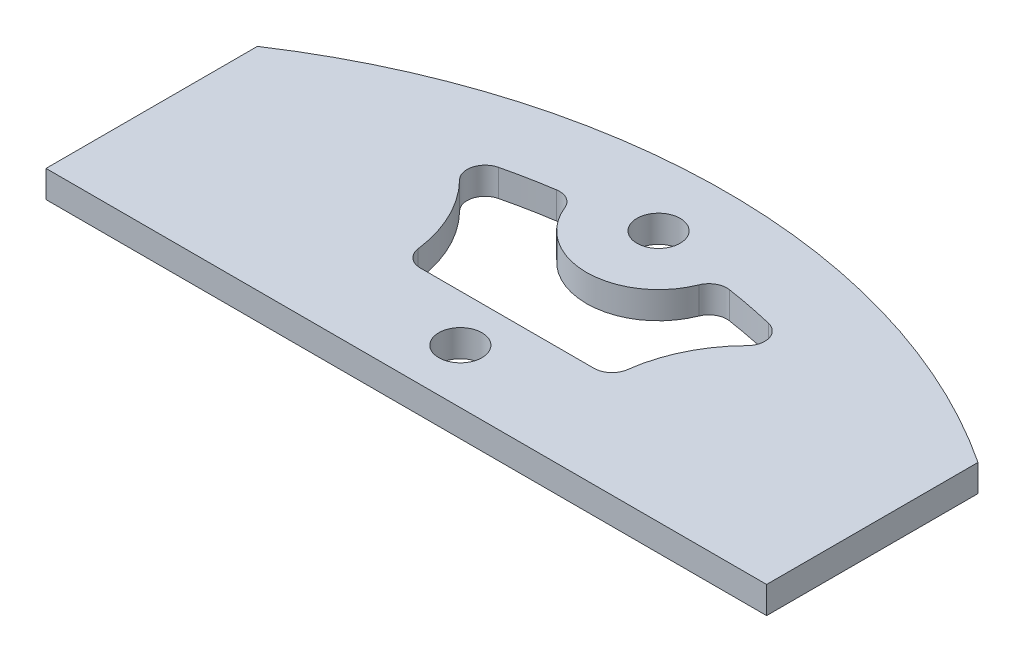
SolidWorks part; units mm, degrees
material "Acrylic (Medium-high impact)"
ref_plane "Front Plane" through (0, 0, 0) normal (0, 0, 1) x (1, 0, 0)
ref_plane "Top Plane" through (0, 0, 0) normal (0, 1, 0) x (1, 0, 0)
ref_plane "Right Plane" through (0, 0, 0) normal (1, 0, 0) x (0, 0, -1)
sketch "Sketch1" plane through (0, 0, 0) normal (0, 1, 0) x (1, 0, 0)
  line L0 (0, -85) -> (-32.4891, -64.8129) construction
  line L1 (0, -85) -> (0, 0) construction
  arc A0 (36.5434, -62.6165) -> (-36.5434, -62.6165) centre (0, 0) ccw
  arc A1 (30.0898, -61.3851) -> (-30.0898, -61.3851) centre (0, -85) ccw
  arc A2 (36.5434, -62.6165) -> (30.0898, -61.3851) centre (34.0231, -58.2982) cw
  arc A3 (-30.0898, -61.3851) -> (-36.5434, -62.6165) centre (-34.0231, -58.2982) cw
  dimension "D1" = 145
  dimension "D2" = 76.5
  dimension "D4" = 5
  dimension "D3" = 85
extrude "Boss-Extrude1" add sketch "Sketch1" along normal blind 3
sketch "Sketch13" plane through (0, 3, 0) normal (0, 1, 0) x (1, 0, 0)
  line L10 (-11.5013, 48.2) -> (11.5013, 48.2)
  line L11 (-9.6388, 48.2) -> (9.6388, 48.2)
  arc A8 (14.9949, 62.2186) -> (15.9519, 58.8715) centre (14.5263, 60.2743) cw
  arc A9 (7.4323, 62.04) -> (9.59, 63.2774) centre (9.2903, 61.3) cw
  arc A10 (9.6388, 48.2) -> (11.623, 49.9486) centre (9.6388, 50.2) ccw
  arc A11 (-9.6388, 48.2) -> (-11.623, 49.9486) centre (-9.6388, 50.2) cw
  arc A28 (-9.59, 63.2774) -> (-7.4323, 62.04) centre (-9.2903, 61.3) cw
  arc A29 (-11.5013, 48.2) -> (-18.8249, 61.1688) centre (-27, 48) ccw
  arc A30 (-7.861, 63.5154) -> (-18.8249, 61.1688) centre (0, 0) ccw
  arc A31 (-7.861, 63.5154) -> (7.861, 63.5154) centre (0, 65) ccw
  arc A32 (18.8249, 61.1688) -> (7.861, 63.5154) centre (0, 0) ccw
  arc A33 (18.8249, 61.1688) -> (11.5013, 48.2) centre (27, 48) ccw
  arc A34 (-11.623, 49.9486) -> (-15.9519, 58.8715) centre (-27, 48) ccw
  arc A35 (-9.59, 63.2774) -> (-14.9949, 62.2186) centre (0, 0) ccw
  arc A36 (-7.4323, 62.04) -> (7.4323, 62.04) centre (0, 65) ccw
  arc A37 (14.9949, 62.2186) -> (9.59, 63.2774) centre (0, 0) ccw
  arc A38 (15.9519, 58.8715) -> (11.623, 49.9486) centre (27, 48) ccw
  arc A39 (-15.9519, 58.8715) -> (-14.9949, 62.2186) centre (-14.5263, 60.2743) cw
  dimension "D2" = 2
  dimension "D1" = 0
extrude "Cut-Extrude14" cut sketch "Sketch13" against normal through all contours A38 A37 A36 A35 A34 L11 region at (0, 3, -55.216)
sketch "Sketch14" plane through (0, 3, 0) normal (0, 1, 0) x (1, 0, 0)
  line L1 (-40, 77) -> (40, 77)
  line L2 (-40, 77) -> (-40, 37)
  line L3 (-40, 37) -> (40, 37)
  line L4 (40, 77) -> (40, 37)
  line L5 (-40, 77) -> (40, 37) construction
  line L6 (-40, 37) -> (40, 77) construction
  arc A0 (-7.4323, 62.04) -> (7.4323, 62.04) centre (0, 65) ccw construction
  point P0 (0, 57)
  dimension "D1" = 80
  dimension "D2" = 40
extrude "Cut-Extrude15" cut sketch "Sketch14" against normal through all flip side to cut
sketch "Sketch15" plane through (0, 3, 0) normal (0, 1, 0) x (1, 0, 0)
  circle A0 centre (0, 65) radius 2.4
  circle A1 centre (0, 43) radius 2.4
  point P5 (0, 0)
  dimension "D1" = 4.8
  dimension "D2" = 22
extrude "Cut-Extrude16" cut sketch "Sketch15" against normal through all
equation "\"smallPulleyTeeth\"= 30"
equation "\"largePulleyTeeth\"= 30"
equation "\"eighthThick\"= 3.0mm"
equation "\"sixteenthThick\" = 1.7mm"
equation "\"quarterThick\"=6.0mm"
equation "\"OD\" = 145mm"
equation "\"puckAngle\" = 60.5deg"
equation "\"D1@Sketch1\"=\"OD\""
equation "\"puckDiam\" = 76.5mm"
equation "\"D2@Sketch1\"=\"puckDiam\""
equation "\"D1@Boss-Extrude1\"=\"eighthThick\""
equation "\"axlePress\" = 5.9mm"
equation "\"press\" = 0.2mm"
equation "\"wheelClear\" = 0.3mm"
equation "\"10-32clear\" = 4.8mm"
equation "\"6-32clear\" = 3.3mm"
equation "\"8-32clear\" = 4.0mm"
equation "\"wheelHeight\" = 22mm"
equation "\"wheelWell\" = 65mm"
equation "\"D1@Sketch3\"=\"wheelWell\""
equation "\"puckDist\" = 85mm"
equation "\"scoopFillet\" = 5mm"
equation "\"4-40clear\" = 3.0mm"
equation "\"D3@Sketch1\"=\"puckDist\""
equation "\"D4@Sketch1\"=\"scoopFillet\""
equation "\"D3@Sketch11\"=\"6-32clear\""
equation "\"D1@Sketch15\"=\"10-32clear\""
